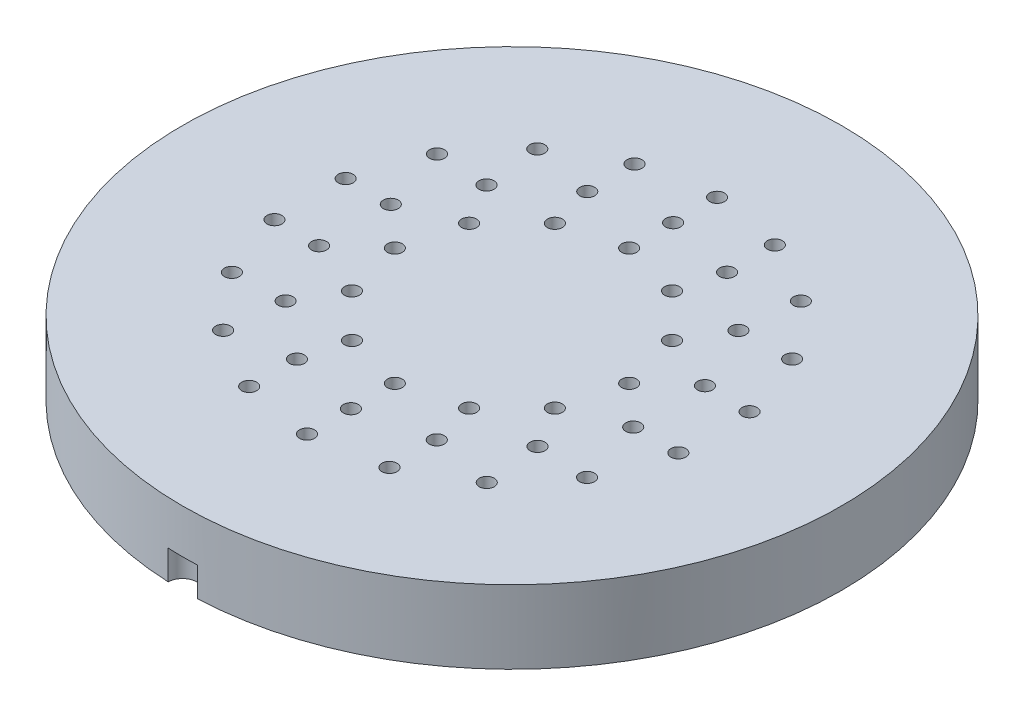
SolidWorks part; units mm, degrees
material "AISI 304"
ref_plane "Front Plane" through (0, 0, 0) normal (0, 0, 1) x (1, 0, 0)
ref_plane "Top Plane" through (0, 0, 0) normal (0, 1, 0) x (1, 0, 0)
ref_plane "Right Plane" through (0, 0, 0) normal (1, 0, 0) x (0, 0, -1)
sketch "Main Shape Profile" plane through (0, 0, 0) normal (0, 0, 1) x (1, 0, 0)
  line L0 (0, 0) -> (0, -36934.052) construction
  line L1 (0, 0) -> (28.575, 0)
  line L2 (28.575, 0) -> (28.575, 6.35)
  line L3 (28.575, 6.35) -> (0, 6.35)
  line L4 (0, 6.35) -> (0, 0)
  dimension "LOX OD" = 57.15
  dimension "LOX Thickness" = 6.35
revolve "Main Shape" add sketch "Main Shape Profile" angle 360 about L0
sketch "Dowel Holes Profile" plane through (0, 0, 0) normal (0, -1, 0) x (1, 0, 0)
  line L0 (0, 28.575) -> (0, -28.575) construction
  circle A0 centre (0, 28.575) radius 1.27
  circle A1 centre (0, -28.575) radius 1.27
  point P4 (0, 0)
  dimension "Dowel Holes Diameter" = 2.54
  dimension "Dowel Placement Inner Diameter" = 57.15
extrude "Dowel Holes" cut sketch "Dowel Holes Profile" against normal blind 2.54
sketch "Injector Holes Profile" plane through (0, 6.35, 0) normal (0, 1, 0) x (1, 0, 0)
  line L0 (0, 0) -> (0, 10.16) construction
  line L1 (0, 10.16) -> (0, 13.97) construction
  line L2 (0, 13.97) -> (0, 17.78) construction
  circle A2 centre (0, 10.16) radius 0.6477
  circle A3 centre (0, 13.97) radius 0.6477
  circle A4 centre (0, 17.78) radius 0.6477
  circle A5 centre (0, 0) radius 10.16 construction
  circle A7 centre (0, 0) radius 17.78 construction
  circle A8 centre (5.08, 8.7988) radius 0.6477
  circle A9 centre (8.7988, 5.08) radius 0.6477
  circle A10 centre (10.16, 0) radius 0.6477
  circle A11 centre (8.7988, -5.08) radius 0.6477
  circle A12 centre (5.08, -8.7988) radius 0.6477
  circle A13 centre (0, -10.16) radius 0.6477
  circle A14 centre (-5.08, -8.7988) radius 0.6477
  circle A15 centre (-8.7988, -5.08) radius 0.6477
  circle A16 centre (-10.16, 0) radius 0.6477
  circle A17 centre (-8.7988, 5.08) radius 0.6477
  circle A18 centre (-5.08, 8.7988) radius 0.6477
  circle A19 centre (6.0614, 12.5865) radius 0.6477
  circle A20 centre (10.9222, 8.7102) radius 0.6477
  circle A21 centre (13.6197, 3.1086) radius 0.6477
  circle A22 centre (13.6197, -3.1086) radius 0.6477
  circle A23 centre (10.9222, -8.7102) radius 0.6477
  circle A24 centre (6.0614, -12.5865) radius 0.6477
  circle A25 centre (0, -13.97) radius 0.6477
  circle A26 centre (-6.0614, -12.5865) radius 0.6477
  circle A27 centre (-10.9222, -8.7102) radius 0.6477
  circle A28 centre (-13.6197, -3.1086) radius 0.6477
  circle A29 centre (-13.6197, 3.1086) radius 0.6477
  circle A30 centre (-10.9222, 8.7102) radius 0.6477
  circle A31 centre (-6.0614, 12.5865) radius 0.6477
  circle A32 centre (6.0811, 16.7077) radius 0.6477
  circle A33 centre (11.4288, 13.6203) radius 0.6477
  circle A34 centre (15.3979, 8.89) radius 0.6477
  circle A35 centre (17.5099, 3.0875) radius 0.6477
  circle A36 centre (17.5099, -3.0875) radius 0.6477
  circle A37 centre (15.3979, -8.89) radius 0.6477
  circle A38 centre (11.4288, -13.6203) radius 0.6477
  circle A39 centre (6.0811, -16.7077) radius 0.6477
  circle A40 centre (0, -17.78) radius 0.6477
  circle A41 centre (-6.0811, -16.7077) radius 0.6477
  circle A42 centre (-11.4288, -13.6203) radius 0.6477
  circle A43 centre (-15.3979, -8.89) radius 0.6477
  circle A44 centre (-17.5099, -3.0875) radius 0.6477
  circle A45 centre (-17.5099, 3.0875) radius 0.6477
  circle A46 centre (-15.3979, 8.89) radius 0.6477
  circle A47 centre (-11.4288, 13.6203) radius 0.6477
  circle A48 centre (-6.0811, 16.7077) radius 0.6477
  point P34 (0, 0)
  point P62 (0, 0)
  point P97 (0, 0)
  dimension "Injector Hole Inner Diameter" = 20.32
  dimension "Injector Hole Outer Diameter" = 35.56
  dimension "LOX Injector Hole Diameter" = 1.2954
  dimension "Inner Ring Num" = 12
  dimension "Middle Ring Num" = 14
  dimension "Outer Ring Num" = 18
hole_wizard "3/8-16 Tapped Hole1" positions "Sketch4" profile "Sketch5" tap size "3/8-16" standard "ANSI Inch" end condition through all
sketch "Sketch4" plane through (0, 6.35, 0) normal (0, 1, 0) x (1, 0, 0)
  point P3 (0, -10.16)
  point P6 (0, -13.97)
  point P9 (0, -17.78)
  point P17 (-5.08, -8.7988)
  point P18 (-8.7988, -5.08)
  point P19 (-10.16, 0)
  point P20 (-8.7988, 5.08)
  point P21 (-5.08, 8.7988)
  point P22 (0, 10.16)
  point P23 (5.08, 8.7988)
  point P24 (8.7988, 5.08)
  point P25 (10.16, 0)
  point P26 (8.7988, -5.08)
  point P27 (5.08, -8.7988)
  point P35 (-6.0614, -12.5865)
  point P36 (-10.9222, -8.7102)
  point P37 (-13.6197, -3.1086)
  point P38 (-13.6197, 3.1086)
  point P39 (-10.9222, 8.7102)
  point P40 (-6.0614, 12.5865)
  point P41 (0, 13.97)
  point P42 (6.0614, 12.5865)
  point P43 (10.9222, 8.7102)
  point P44 (13.6197, 3.1086)
  point P45 (13.6197, -3.1086)
  point P46 (10.9222, -8.7102)
  point P47 (6.0614, -12.5865)
  point P55 (-6.0811, -16.7077)
  point P56 (-11.4288, -13.6203)
  point P57 (-15.3979, -8.89)
  point P58 (-17.5099, -3.0875)
  point P59 (-17.5099, 3.0875)
  point P60 (-15.3979, 8.89)
  point P61 (-11.4288, 13.6203)
  point P62 (-6.0811, 16.7077)
  point P63 (0, 17.78)
  point P64 (6.0811, 16.7077)
  point P65 (11.4288, 13.6203)
  point P66 (15.3979, 8.89)
  point P67 (17.5099, 3.0875)
  point P68 (17.5099, -3.0875)
  point P69 (15.3979, -8.89)
  point P70 (11.4288, -13.6203)
  point P71 (6.0811, -16.7077)
  dimension "D1" = 12
  dimension "D2" = 14
  dimension "D3" = 18
sketch "Sketch5" plane through (0, 6.35, 10.16) normal (1, 0, 0) x (0, 0, 1)
  line L0 (0, 0) -> (0, 6.35)
  line L1 (0, 6.35) -> (0.6477, 6.35)
  line L2 (0.6477, 6.35) -> (0.6477, 0)
  line L5 (0.6477, 0) -> (0, 0)
  line L11 (0, -6.35) -> (0, 107.95) construction
  dimension "Thru Tap Drill Dia." = 1.2954
  dimension "Thru Tap Drill Depth" = 6.35
equation "\"D1@Sketch4\"= \"Inner Ring Num@Injector Holes Profile\""
equation "\"D2@Sketch4\"= \"Middle Ring Num@Injector Holes Profile\""
equation "\"D3@Sketch4\"= \"Outer Ring Num@Injector Holes Profile\""
equation "\"Thru Tap Drill Dia.@Sketch5\"= \"LOX Injector Hole Diameter@Injector Holes Profile\""
